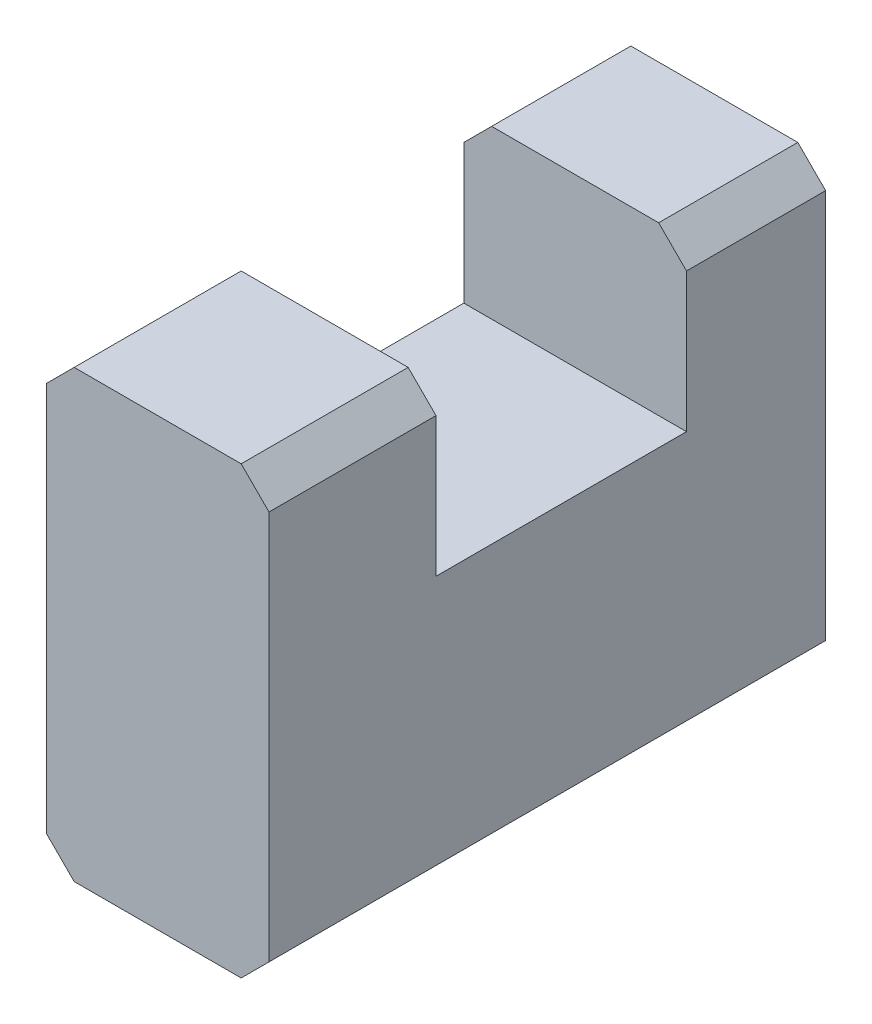
SolidWorks part; units mm, degrees
ref_plane "Front Plane" through (0, 0, 0) normal (0, 0, 1) x (1, 0, 0)
ref_plane "Top Plane" through (0, 0, 0) normal (0, 1, 0) x (1, 0, 0)
ref_plane "Right Plane" through (0, 0, 0) normal (1, 0, 0) x (0, 0, -1)
sketch "Sketch1" plane through (0, 0, 0) normal (0, 0, 1) x (1, 0, 0)
  line L0 (0, 4) -> (0, -4) construction
  line L1 (-2, 4) -> (2, 4)
  line L2 (-2, 4) -> (-2, -4)
  line L3 (-2, -4) -> (2, -4)
  line L4 (2, 4) -> (2, -4)
  line L5 (-2, 0) -> (2, 0) construction
  dimension "D1" = 4
  dimension "D2" = 8
extrude "Boss-Extrude1" add sketch "Sketch1" along normal blind 10
chamfer "Chamfer1" distance 0.5 angle 45 4 edges at (-2, -4, 5) (2, -4, 5) (2, 4, 5) (-2, 4, 5)
sketch "Sketch2" plane through (0, 0, 0) normal (1, 0, 0) x (0, 0, -1)
  line L0 (-2.5, 4) -> (-2.5, 1)
  line L2 (-2.5, 1) -> (-7, 1)
  line L3 (-7, 1) -> (-7, 4)
  line L4 (-10, 4) -> (0, 4) construction
  line L5 (-7, 4) -> (-2.5, 4)
  line L6 (0, 4) -> (0, -4) construction
  dimension "D1" = 4.5
  dimension "D2" = 3
  dimension "D3" = 2.5
extrude "Cut-Extrude1" cut sketch "Sketch2" against normal through all both and the other way through all
